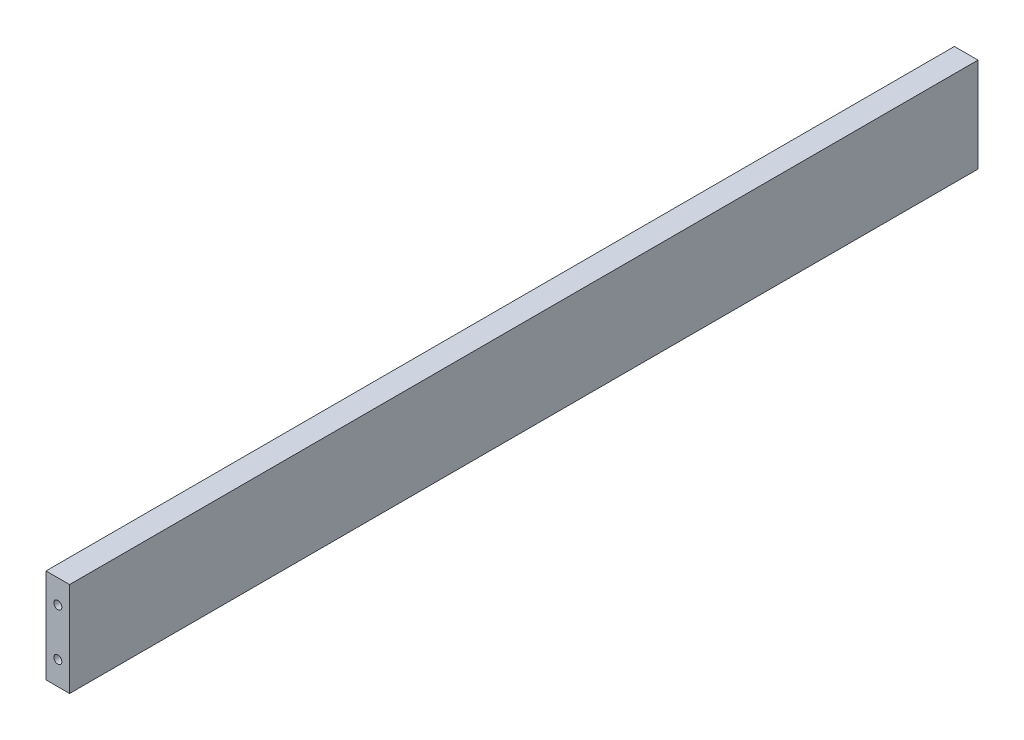
SolidWorks part; units mm, degrees
material "6063-T5"
ref_plane "Front Plane" through (0, 0, 0) normal (0, 0, 1) x (1, 0, 0)
ref_plane "Top Plane" through (0, 0, 0) normal (0, 1, 0) x (1, 0, 0)
ref_plane "Right Plane" through (0, 0, 0) normal (1, 0, 0) x (0, 0, -1)
sketch "Sketch1" plane through (0, 0, 0) normal (0, 0, 1) x (1, 0, 0)
  line L1 (10, -40) -> (-10, -40)
  line L2 (10, -40) -> (10, 40)
  line L3 (10, 40) -> (-10, 40)
  line L4 (-10, -40) -> (-10, 40)
  line L5 (10, -40) -> (-10, 40) construction
  line L6 (10, 40) -> (-10, -40) construction
  point P0 (0, 0)
  dimension "D1" = 80
  dimension "D2" = 20
extrude "Boss-Extrude1" add sketch "Sketch1" against normal blind 770
sketch "Sketch2" plane through (0, 0, 0) normal (0, 0, 1) x (1, 0, 0)
  line L0 (10, 40) -> (-10, 40) construction
  line L1 (-10, -40) -> (10, -40) construction
  point P0 (0, 20)
  point P1 (0, -20)
  point P2 (0, 40)
  dimension "D1" = 20
  dimension "D2" = 20
hole_wizard "M8 Tapped Hole1" positions "3DSketch2" profile "Sketch4" tap size "M8" standard "ISO"
sketch3d "3DSketch2"
  point P0 (0, 20, 0)
  point P3 (0, -20, 0)
sketch "Sketch4" plane through (0, 20, 0) normal (1, 0, 0) x (0, -1, 0)
  line L0 (0, 0) -> (0, 27.7929)
  line L1 (0, 27.7929) -> (3.4, 25.75)
  line L2 (3.4, 25.75) -> (3.4, 0)
  line L5 (3.4, 0) -> (0, 0)
  line L10 (0, 27.7929) -> (-3.4, 25.75) construction
  line L11 (0, -6.35) -> (0, 107.95) construction
  dimension "Tap Drill Dia." = 6.8
  dimension "Tap Drill Depth" = 25.75
  dimension "Drill Angle" = 118
sketch "Sketch5" plane through (0, 0, -770) normal (0, 0, -1) x (-1, 0, 0)
  line L0 (0, 40) -> (0, -40) construction
  line L1 (-10, 40) -> (10, 40) construction
  line L2 (10, -40) -> (-10, -40) construction
  point P6 (0, 20)
  point P7 (0, -20)
  dimension "D1" = 20
  dimension "D2" = 20
hole_wizard "M8 Tapped Hole3" positions "3DSketch4" profile "Sketch7" tap size "M8" standard "ISO"
sketch3d "3DSketch4"
  point P5 (0, 20, -770)
  point P8 (0, -20, -770)
sketch "Sketch7" plane through (0, 20, -770) normal (1, 0, 0) x (0, 1, 0)
  line L0 (0, 0) -> (0, 27.7929)
  line L1 (0, 27.7929) -> (3.4, 25.75)
  line L2 (3.4, 25.75) -> (3.4, 0)
  line L5 (3.4, 0) -> (0, 0)
  line L10 (0, 27.7929) -> (-3.4, 25.75) construction
  line L11 (0, -6.35) -> (0, 107.95) construction
  dimension "Tap Drill Dia." = 6.8
  dimension "Tap Drill Depth" = 25.75
  dimension "Drill Angle" = 118
